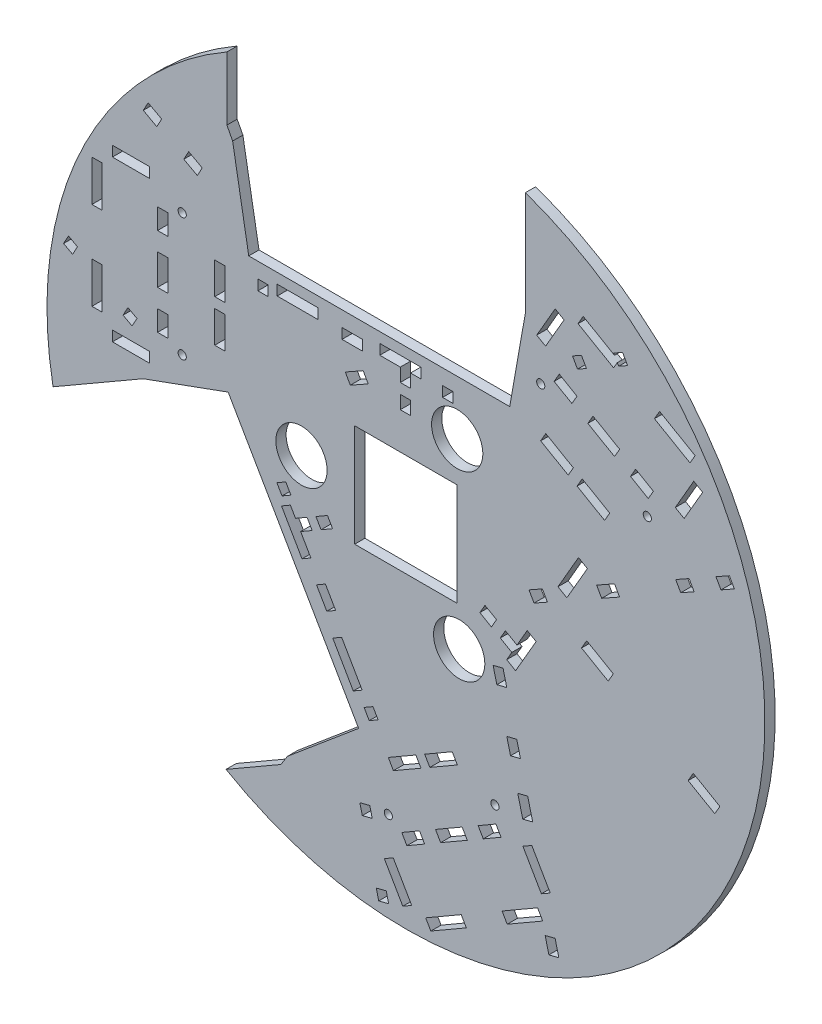
SolidWorks part; units mm, degrees
material "Balsa"
ref_plane "Plan de face" through (0, 0, 0) normal (0, 0, 1) x (1, 0, 0)
ref_plane "Plan de dessus" through (0, 0, 0) normal (0, 1, 0) x (1, 0, 0)
ref_plane "Plan de droite" through (0, 0, 0) normal (1, 0, 0) x (0, 0, -1)
sketch "Esquisse1" plane through (0, 0, 0) normal (0, 0, 1) x (1, 0, 0)
  circle A0 centre (148.0804, -12.1102) radius 175
  dimension "D1" = 350
extrude "Boss.-Extru.1" add sketch "Esquisse1" along normal blind 5
sketch "Esquisse2" plane through (0, 0, 5) normal (0, 0, 1) x (1, 0, 0)
  line L0 (135.3118, 53.7774) -> (135.3118, 48.7774)
  line L1 (5, 72.2774) -> (23, 72.2774)
  line L2 (5, 72.2774) -> (5, 67.2774)
  line L3 (5, 67.2774) -> (23, 67.2774)
  line L4 (23, 72.2774) -> (23, 67.2774)
  line L5 (-5, 62.2774) -> (0, 62.2774)
  line L6 (-5, 62.2774) -> (-5, 42.2774)
  line L7 (-5, 42.2774) -> (0, 42.2774)
  line L8 (0, 62.2774) -> (0, 42.2774)
  line L9 (-5, 19.2774) -> (0, 19.2774)
  line L10 (-5, 19.2774) -> (-5, -0.7226)
  line L11 (-5, -0.7226) -> (0, -0.7226)
  line L12 (0, 19.2774) -> (0, -0.7226)
  line L13 (5, -5.7226) -> (23, -5.7226)
  line L14 (5, -5.7226) -> (5, -10.7226)
  line L15 (5, -10.7226) -> (23, -10.7226)
  line L16 (23, -5.7226) -> (23, -10.7226)
  line L17 (27, 14.2774) -> (32, 14.2774)
  line L18 (27, 14.2774) -> (27, 4.2774)
  line L19 (27, 4.2774) -> (32, 4.2774)
  line L20 (32, 14.2774) -> (32, 4.2774)
  line L21 (27, 38.2774) -> (32, 38.2774)
  line L22 (27, 38.2774) -> (27, 23.2774)
  line L23 (27, 23.2774) -> (32, 23.2774)
  line L24 (32, 38.2774) -> (32, 23.2774)
  line L25 (27, 57.2774) -> (32, 57.2774)
  line L26 (27, 57.2774) -> (27, 47.2774)
  line L27 (27, 47.2774) -> (32, 47.2774)
  line L28 (32, 57.2774) -> (32, 47.2774)
  line L29 (54.86, 48.7774) -> (59.86, 48.7774)
  line L30 (54.86, 48.7774) -> (54.86, 33.2774)
  line L31 (54.86, 33.2774) -> (59.86, 33.2774)
  line L32 (59.86, 48.7774) -> (59.86, 33.2774)
  line L33 (54.86, 28.2774) -> (59.86, 28.2774)
  line L34 (54.86, 28.2774) -> (54.86, 12.7774)
  line L35 (54.86, 12.7774) -> (59.86, 12.7774)
  line L36 (59.86, 28.2774) -> (59.86, 12.7774)
  line L37 (85.3118, 53.7774) -> (105.3118, 53.7774)
  line L38 (85.3118, 53.7774) -> (85.3118, 48.7774)
  line L39 (85.3118, 48.7774) -> (105.3118, 48.7774)
  line L40 (105.3118, 53.7774) -> (105.3118, 48.7774)
  line L41 (145.3118, 37.2774) -> (150.3118, 37.2774)
  line L42 (145.3118, 37.2774) -> (145.3118, 30.7774)
  line L43 (145.3118, 30.7774) -> (150.3118, 30.7774)
  line L44 (150.3118, 37.2774) -> (150.3118, 30.7774)
  line L45 (135.3118, 48.7774) -> (145.3118, 48.7774)
  line L46 (155.3118, 48.7774) -> (135.3118, 48.7774) construction
  line L47 (145.3118, 48.7774) -> (145.3118, 42.2774)
  line L48 (145.3118, 42.2774) -> (150.3118, 42.2774)
  line L49 (150.3118, 42.2774) -> (150.3118, 48.7774)
  line L50 (150.3118, 48.7774) -> (155.3118, 48.7774)
  line L51 (155.3118, 48.7774) -> (155.3118, 53.7774)
  line L52 (155.3118, 53.7774) -> (135.3118, 53.7774)
  line L53 (292.7025, 69.6073) -> (283.7025, 54.0188)
  line L54 (292.7025, 69.6073) -> (288.3723, 72.1073)
  line L55 (288.3723, 72.1073) -> (279.3723, 56.5188)
  line L56 (283.7025, 54.0188) -> (279.3723, 56.5188)
  line L57 (289.0422, 83.2676) -> (286.5422, 78.9374)
  line L58 (289.0422, 83.2676) -> (271.7217, 93.2676)
  line L59 (271.7217, 93.2676) -> (269.2217, 88.9374)
  line L60 (286.5422, 78.9374) -> (269.2217, 88.9374)
  line L61 (251.8031, 104.7676) -> (249.3031, 100.4374)
  line L62 (251.8031, 104.7676) -> (234.4826, 114.7676)
  line L63 (234.4826, 114.7676) -> (231.9826, 110.4374)
  line L64 (249.3031, 100.4374) -> (231.9826, 110.4374)
  line L65 (225.1525, 108.6073) -> (216.1525, 93.0188)
  line L66 (225.1525, 108.6073) -> (220.8223, 111.1073)
  line L67 (220.8223, 111.1073) -> (211.8223, 95.5188)
  line L68 (216.1525, 93.0188) -> (211.8223, 95.5188)
  line L69 (231.473, 79.5547) -> (228.973, 75.2246)
  line L70 (231.473, 79.5547) -> (222.8127, 84.5547)
  line L71 (222.8127, 84.5547) -> (220.3127, 80.2246)
  line L72 (228.973, 75.2246) -> (220.3127, 80.2246)
  line L73 (252.2576, 67.5547) -> (249.7576, 63.2246)
  line L74 (252.2576, 67.5547) -> (239.2672, 75.0547)
  line L75 (239.2672, 75.0547) -> (236.7672, 70.7246)
  line L76 (249.7576, 63.2246) -> (236.7672, 70.7246)
  line L77 (268.7121, 58.0547) -> (266.2121, 53.7246)
  line L78 (268.7121, 58.0547) -> (260.0518, 63.0547)
  line L79 (260.0518, 63.0547) -> (257.5518, 58.7246)
  line L80 (266.2121, 53.7246) -> (257.5518, 58.7246)
  line L81 (247.4209, 38.1773) -> (244.9209, 33.8472)
  line L82 (247.4209, 38.1773) -> (233.9975, 45.9273)
  line L83 (233.9975, 45.9273) -> (231.4975, 41.5972)
  line L84 (244.9209, 33.8472) -> (231.4975, 41.5972)
  line L85 (229.6673, 48.4273) -> (227.1673, 44.0972)
  line L86 (229.6673, 48.4273) -> (216.2439, 56.1773)
  line L87 (216.2439, 56.1773) -> (213.7439, 51.8472)
  line L88 (227.1673, 44.0972) -> (213.7439, 51.8472)
  line L89 (211.5251, -33.996) -> (207.195, -31.496)
  line L90 (236.5251, 9.3053) -> (226.5251, -8.0153)
  line L91 (236.5251, 9.3053) -> (232.195, 11.8053)
  line L92 (232.195, 11.8053) -> (222.195, -5.5153)
  line L93 (226.5251, -8.0153) -> (222.195, -5.5153)
  line L94 (192.2357, -34.4063) -> (189.7357, -38.7364)
  line L95 (192.2357, -34.4063) -> (186.6065, -31.1563)
  line L96 (186.6065, -31.1563) -> (184.1065, -35.4864)
  line L97 (189.7357, -38.7364) -> (184.1065, -35.4864)
  line L98 (207.195, -31.496) -> (202.195, -40.1563)
  line L99 (202.195, -40.1563) -> (196.5658, -36.9063)
  line L100 (196.5658, -36.9063) -> (194.0658, -41.2364)
  line L101 (194.0658, -41.2364) -> (199.695, -44.4864)
  line L102 (199.695, -44.4864) -> (197.195, -48.8165)
  line L103 (197.195, -48.8165) -> (201.5251, -51.3165)
  line L104 (201.5251, -51.3165) -> (211.5251, -33.996)
  line L105 (146.5388, -178.2153) -> (137.5388, -162.6268)
  line L106 (146.5388, -178.2153) -> (150.869, -175.7153)
  line L107 (150.869, -175.7153) -> (141.869, -160.1268)
  line L108 (137.5388, -162.6268) -> (141.869, -160.1268)
  line L109 (160.1991, -181.8755) -> (157.6991, -177.5454)
  line L110 (160.1991, -181.8755) -> (177.5196, -171.8755)
  line L111 (177.5196, -171.8755) -> (175.0196, -167.5454)
  line L112 (157.6991, -177.5454) -> (175.0196, -167.5454)
  line L113 (197.4382, -160.3755) -> (194.9382, -156.0454)
  line L114 (197.4382, -160.3755) -> (214.7587, -150.3755)
  line L115 (214.7587, -150.3755) -> (212.2587, -146.0454)
  line L116 (194.9382, -156.0454) -> (212.2587, -146.0454)
  line L117 (214.0888, -139.2153) -> (205.0888, -123.6268)
  line L118 (214.0888, -139.2153) -> (218.4189, -136.7153)
  line L119 (218.4189, -136.7153) -> (209.4189, -121.1268)
  line L120 (205.0888, -123.6268) -> (209.4189, -121.1268)
  line L121 (185.7683, -130.1627) -> (183.2683, -125.8326)
  line L122 (185.7683, -130.1627) -> (194.4286, -125.1627)
  line L123 (194.4286, -125.1627) -> (191.9286, -120.8326)
  line L124 (183.2683, -125.8326) -> (191.9286, -120.8326)
  line L125 (164.9837, -142.1627) -> (162.4837, -137.8326)
  line L126 (164.9837, -142.1627) -> (177.9741, -134.6627)
  line L127 (177.9741, -134.6627) -> (175.4741, -130.3326)
  line L128 (162.4837, -137.8326) -> (175.4741, -130.3326)
  line L129 (148.5292, -151.6627) -> (146.0292, -147.3326)
  line L130 (148.5292, -151.6627) -> (157.1895, -146.6627)
  line L131 (157.1895, -146.6627) -> (154.6895, -142.3326)
  line L132 (146.0292, -147.3326) -> (154.6895, -142.3326)
  line L133 (141.9604, -123.2852) -> (139.4604, -118.9551)
  line L134 (141.9604, -123.2852) -> (155.3838, -115.5352)
  line L135 (155.3838, -115.5352) -> (152.8838, -111.2051)
  line L136 (139.4604, -118.9551) -> (152.8838, -111.2051)
  line L137 (159.7139, -113.0352) -> (157.2139, -108.7051)
  line L138 (159.7139, -113.0352) -> (173.1373, -105.2852)
  line L139 (173.1373, -105.2852) -> (170.6373, -100.9551)
  line L140 (157.2139, -108.7051) -> (170.6373, -100.9551)
  line L141 (97.4044, -56.1119) -> (101.7345, -53.6119)
  line L142 (122.4044, -99.4132) -> (112.4044, -82.0927)
  line L143 (122.4044, -99.4132) -> (126.7345, -96.9132)
  line L144 (126.7345, -96.9132) -> (116.7345, -79.5927)
  line L145 (112.4044, -82.0927) -> (116.7345, -79.5927)
  line L146 (106.6938, -39.2017) -> (104.1938, -34.8716)
  line L147 (106.6938, -39.2017) -> (112.323, -35.9517)
  line L148 (112.323, -35.9517) -> (109.823, -31.6216)
  line L149 (104.1938, -34.8716) -> (109.823, -31.6216)
  line L150 (101.7345, -53.6119) -> (96.7345, -44.9517)
  line L151 (96.7345, -44.9517) -> (102.3637, -41.7017)
  line L152 (102.3637, -41.7017) -> (99.8637, -37.3716)
  line L153 (99.8637, -37.3716) -> (94.2345, -40.6216)
  line L154 (94.2345, -40.6216) -> (91.7345, -36.2914)
  line L155 (91.7345, -36.2914) -> (87.4044, -38.7914)
  line L156 (87.4044, -38.7914) -> (97.4044, -56.1119)
  line L157 (135.3118, 53.7774) -> (135.3118, 48.7774) construction
  line L158 (105.3118, 53.7774) -> (135.3118, 53.7774) construction
  point P83 (148.0804, -12.1102)
  point P192 (148.0804, -12.1102)
  point P193 (148.0804, -12.1102)
  dimension "D1" = 3
extrude "Enlèv. mat.-Extru.1" cut sketch "Esquisse2" against normal blind 5
sketch "Esquisse6" plane through (0, 0, 5) normal (0, 0, 1) x (1, 0, 0)
  line L0 (93.9998, -7.2151) -> (100.2998, -18.127) construction
  line L1 (206.3213, 102.2219) -> (206.3213, 185.5637)
  line L2 (123.0804, -37.1102) -> (173.0804, -37.1102)
  line L3 (123.0804, -37.1102) -> (123.0804, 12.8898)
  line L4 (123.0804, 12.8898) -> (173.0804, 12.8898)
  line L5 (173.0804, -37.1102) -> (173.0804, 12.8898)
  line L6 (123.0804, -37.1102) -> (173.0804, 12.8898) construction
  line L7 (123.0804, 12.8898) -> (173.0804, -37.1102) construction
  line L8 (206.3213, 185.5637) -> (60.7972, 185.5637)
  line L9 (71.4438, 58.7774) -> (63.5848, 103.3483)
  line L10 (71.4438, 58.7774) -> (198.6608, 58.7774)
  line L11 (198.6608, 58.7774) -> (206.3213, 102.2219)
  line L12 (60.7972, 185.5637) -> (60.7972, 108.6824)
  line L13 (19.9456, -18.8381) -> (-52.2306, -60.5091)
  line L14 (-52.2306, -60.5091) -> (20.5314, -186.5366)
  line L15 (63.5848, 103.3483) -> (60.7972, 108.6824)
  line L16 (125.0083, -113.9232) -> (90.3383, -143.0148)
  line L17 (125.0083, -113.9232) -> (61.3998, -3.7501)
  line L18 (61.3998, -3.7501) -> (19.9456, -18.8381)
  line L20 (236.1714, -21.3074) -> (249.1617, -28.8074)
  line L21 (236.1714, -21.3074) -> (233.6714, -25.6375)
  line L22 (249.1617, -28.8074) -> (246.6617, -33.1375)
  line L23 (233.6714, -25.6375) -> (246.6617, -33.1375)
  line L24 (288.1329, -51.3074) -> (301.1233, -58.8074)
  line L25 (288.1329, -51.3074) -> (285.6329, -55.6375)
  line L26 (301.1233, -58.8074) -> (298.6233, -63.1375)
  line L27 (285.6329, -55.6375) -> (298.6233, -63.1375)
  line L28 (226.5251, -8.0153) -> (236.5251, 9.3053) construction
  line L29 (279.3723, 56.5188) -> (283.7025, 54.0188) construction
  line L31 (64.5427, 103.6743) -> (63.0102, 106.6067) construction
  line L32 (20.5314, -186.5366) -> (87.1126, -148.0959)
  line L33 (90.3383, -143.0148) -> (87.1126, -148.0959)
  circle A0 centre (173.06, 32.2774) radius 12.5
  circle A1 centre (174.0314, -55.9369) radius 12.5
  circle A2 centre (97.1498, -12.671) radius 12.5
  point P2 (148.0804, -12.1102)
  point P8 (148.0804, -12.1102)
  point P10 (148.0804, -12.1102)
  point P35 (148.0804, -12.1102)
  point P48 (148.0804, -12.1102)
  dimension "D12" = 25
  dimension "D3" = 50
  dimension "D4" = 50
  dimension "D5" = 70.8876
  dimension "D6" = 50.5804
  dimension "D7" = 127.217
  dimension "D8" = 100
  dimension "D9" = 100
  dimension "D10" = 145.5241
  dimension "D11" = 43.4444
  dimension "D13" = 5
  dimension "D14" = 15
  dimension "D15" = 15
  dimension "D16" = 45
  dimension "D17" = 15
  dimension "D18" = 89
  dimension "D19" = 2
  dimension "D20" = 1
  dimension "D1" = 3
extrude "Enlèv. mat.-Extru.6" cut sketch "Esquisse6" against normal blind 5
hole_wizard "Trous de centrage Ø4.0mm1" positions "Esquisse7" profile "Esquisse8" hole size "Ø4.0" standard "Ansi Metric" end condition through all
sketch "Esquisse7" plane through (148.0804, -12.1102, -78) normal (0, 0, -1) x (1, 0, 0)
  point P0 (65.7012, -88.0226)
  point P3 (117.6627, -58.0226)
  point P6 (-109.0804, -72.8876)
  point P9 (-109.0804, -12.8876)
  point P12 (-8.5823, 130.9102)
  point P15 (43.3792, 100.9102)
sketch "Esquisse8" plane through (213.7816, 75.9124, -78) normal (1, 0, 0) x (0, 1, 0)
  line L0 (0, 0) -> (0, 83)
  line L1 (0, 83) -> (2, 83)
  line L2 (2, 83) -> (2, 0)
  line L3 (2, 0) -> (0, 0)
  line L4 (0, -6.35) -> (0, 107.95) construction
  dimension "Diamètre du perçage jusqu'au prochain" = 4
  dimension "Profondeur du perçage jusqu'au prochain" = 83
sketch "Esquisse9" plane through (0, 0, 5) normal (0, 0, 1) x (1, 0, 0)
  line L0 (301.6473, 32.8747) -> (299.2005, 37.2351)
  line L1 (301.6473, 32.8747) -> (308.1879, 36.5449)
  line L2 (299.2005, 37.2351) -> (305.7411, 40.9053)
  line L3 (308.1879, 36.5449) -> (305.7411, 40.9053)
  line L4 (282.0254, 21.8642) -> (279.5786, 26.2246)
  line L5 (282.0254, 21.8642) -> (288.566, 25.5344)
  line L6 (279.5786, 26.2246) -> (286.1192, 29.8948)
  line L7 (288.566, 25.5344) -> (286.1192, 29.8948)
  line L8 (252.2089, 5.133) -> (249.7621, 9.4935)
  line L9 (252.2089, 5.133) -> (243.488, 0.2395)
  line L10 (249.7621, 9.4935) -> (241.0412, 4.5999)
  line L11 (243.488, 0.2395) -> (241.0412, 4.5999)
  line L12 (214.6084, -10.2326) -> (217.0552, -14.593)
  line L13 (214.6084, -10.2326) -> (208.0678, -13.9027)
  line L14 (217.0552, -14.593) -> (210.5146, -18.2632)
  line L15 (208.0678, -13.9027) -> (210.5146, -18.2632)
  line L16 (217.0552, -14.593) -> (243.488, 0.2395) construction
  line L17 (214.6084, -10.2326) -> (217.0552, -14.593) construction
  line L18 (256.1275, 104.7997) -> (251.7671, 102.3529)
  line L19 (256.1275, 104.7997) -> (253.6807, 109.1601)
  line L20 (251.7671, 102.3529) -> (249.3203, 106.7133)
  line L21 (253.6807, 109.1601) -> (249.3203, 106.7133)
  line L22 (236.0696, 93.5445) -> (231.7091, 91.0977)
  line L23 (236.0696, 93.5445) -> (233.6228, 97.9049)
  line L24 (231.7091, 91.0977) -> (229.2624, 95.4581)
  line L25 (233.6228, 97.9049) -> (229.2624, 95.4581)
  line L26 (129.6754, 33.8428) -> (120.9546, 28.9492)
  line L27 (129.6754, 33.8428) -> (127.2286, 38.2032)
  line L28 (120.9546, 28.9492) -> (118.5078, 33.3096)
  line L29 (127.2286, 38.2032) -> (118.5078, 33.3096)
  line L30 (256.1275, 104.7997) -> (120.9546, 28.9492) construction
  line L31 (301.6473, 32.8747) -> (217.0552, -14.593) construction
  line L32 (-16.4384, 23.2791) -> (-12.0459, 20.8904)
  line L33 (-16.4384, 23.2791) -> (-18.8272, 18.8866)
  line L34 (-12.0459, 20.8904) -> (-14.4347, 16.4979)
  line L35 (-18.8272, 18.8866) -> (-14.4347, 16.4979)
  line L36 (12.552, 7.5136) -> (16.9445, 5.1249)
  line L37 (12.552, 7.5136) -> (10.1633, 3.1211)
  line L38 (16.9445, 5.1249) -> (14.5558, 0.7324)
  line L39 (10.1633, 3.1211) -> (14.5558, 0.7324)
  line L42 (-26.9196, -12.1102) -> (148.0804, -12.1102) construction
  line L44 (22.4127, 98.9071) -> (29.0015, 95.324)
  line L45 (22.4127, 98.9071) -> (20.024, 94.5146)
  line L46 (29.0015, 95.324) -> (26.6128, 90.9315)
  line L47 (20.024, 94.5146) -> (26.6128, 90.9315)
  line L48 (42.179, 88.1579) -> (48.7677, 84.5748)
  line L49 (42.179, 88.1579) -> (39.7903, 83.7654)
  line L50 (48.7677, 84.5748) -> (46.379, 80.1823)
  line L51 (39.7903, 83.7654) -> (46.379, 80.1823)
  line L53 (148.0804, -12.1102) -> (9.6568, -109.2191) construction
  line L55 (129.7636, 187.6323) -> (148.0804, -12.1102) construction
  arc A0 (60.3638, -163.5394) -> (206.3213, 152.9141) centre (148.0804, -12.1102) ccw construction
  line B0 (154.106, -73.5915) -> (185.6214, -199.5155) construction
  line B1 (126.7996, -149.8343) -> (125.5857, -144.9839)
  line B2 (130.4361, -143.77) -> (125.5857, -144.9839)
  line B3 (131.65, -148.6204) -> (126.7996, -149.8343)
  line B4 (131.65, -148.6204) -> (130.4361, -143.77)
  line B5 (134.8115, -181.8469) -> (133.5976, -176.9965)
  line B6 (138.448, -175.7826) -> (133.5976, -176.9965)
  line B7 (139.6619, -180.633) -> (134.8115, -181.8469)
  line B8 (139.6619, -180.633) -> (138.448, -175.7826)
  line B9 (190.562, -54.5014) -> (195.4124, -53.2875)
  line B10 (197.2333, -60.5631) -> (195.4124, -53.2875)
  line B11 (192.3829, -61.777) -> (190.562, -54.5014)
  line B12 (192.3829, -61.777) -> (197.2333, -60.5631)
  line B13 (202.089, -79.9647) -> (197.2386, -81.1786)
  line B14 (199.0595, -88.4542) -> (197.2386, -81.1786)
  line B15 (203.9099, -87.2403) -> (202.089, -79.9647)
  line B16 (203.9099, -87.2403) -> (199.0595, -88.4542)
  line B17 (222.6043, -161.9364) -> (217.7539, -163.1503)
  line B18 (215.933, -155.8747) -> (217.7539, -163.1503)
  line B19 (220.7834, -154.6608) -> (222.6043, -161.9364)
  line B20 (220.7834, -154.6608) -> (215.933, -155.8747)
  dimension "D9" = 170.2546
  dimension "D1" = 10
  dimension "D2" = 5
  dimension "D3" = 7.5
  dimension "D4" = 10
  dimension "D5" = 7.5
  dimension "D6" = 7.5
  dimension "D7" = 5
  dimension "D8" = 117
  dimension "D10" = 167.3371
  dimension "D11" = 69
  dimension "D12" = 35.051
  dimension "D13" = 30.31
  dimension "D14" = 5
sketch_block_instance "Bloc1-1"
sketch_block "Bloc1"
extrude "Holes catchers of glass" cut sketch "Esquisse9" against normal blind 10
sketch "Esquisse10" plane through (0, 0, 5) normal (0, 0, 1) x (1, 0, 0)
  line L0 (89.4961, -27.6144) -> (91.9961, -31.9445)
  line L1 (89.4961, -27.6144) -> (85.1672, -30.1137)
  line L2 (91.9961, -31.9445) -> (87.6672, -34.4438)
  line L3 (85.1672, -30.1137) -> (87.6672, -34.4438)
  dimension "D1" = 4.9986
extrude "Holes boards servo" cut sketch "Esquisse10" against normal blind 10
sketch "Esquisse11" plane through (0, 0, 5) normal (0, 0, 1) x (1, 0, 0)
  line L0 (109.4829, -72.2325) -> (104.4829, -63.5722)
  line L1 (109.4829, -72.2325) -> (113.813, -69.7325)
  line L2 (104.4829, -63.5722) -> (108.813, -61.0722)
  line L3 (113.813, -69.7325) -> (108.813, -61.0722)
  line L4 (125.166, -99.3964) -> (90.166, -38.7747) construction
  line L6 (116.7345, -79.5927) -> (112.4044, -82.0927) construction
  line L7 (130.166, -108.0567) -> (134.4961, -105.5567)
  line L8 (130.166, -108.0567) -> (127.666, -103.7266)
  line L9 (134.4961, -105.5567) -> (131.9961, -101.2266)
  line L10 (127.666, -103.7266) -> (131.9961, -101.2266)
  line L11 (207.4302, -101.3064) -> (209.8581, -111.0072)
  line L12 (170.9253, 51.2774) -> (165.9253, 51.2774)
  line L13 (170.9253, 51.2774) -> (170.9253, 46.2774)
  line L14 (170.9253, 46.2774) -> (165.9253, 46.2774)
  line L15 (165.9253, 51.2774) -> (165.9253, 46.2774)
  line L16 (126.9253, 51.2774) -> (116.9253, 51.2774)
  line L17 (126.9253, 51.2774) -> (126.9253, 46.2774)
  line L18 (126.9253, 46.2774) -> (116.9253, 46.2774)
  line L19 (116.9253, 51.2774) -> (116.9253, 46.2774)
  line L20 (80.9253, 51.2774) -> (75.9253, 51.2774)
  line L21 (80.9253, 51.2774) -> (80.9253, 46.2774)
  line L22 (80.9253, 46.2774) -> (75.9253, 46.2774)
  line L23 (75.9253, 51.2774) -> (75.9253, 46.2774)
  line L24 (207.4302, -101.3064) -> (202.5798, -102.5203)
  line L25 (209.8581, -111.0072) -> (205.0077, -112.2211)
  line L26 (202.5798, -102.5203) -> (205.0077, -112.2211)
  line L27 (203.9099, -87.2403) -> (202.089, -79.9647) construction
  line L28 (220.7834, -154.6608) -> (215.933, -155.8747) construction
  dimension "D1" = 10
  dimension "D2" = 10
  dimension "D3" = 5
  dimension "D4" = 5
  dimension "D5" = 5
  dimension "D6" = 10
  dimension "D7" = 45
extrude "Enlèv. mat.-Extru.7" cut sketch "Esquisse11" against normal blind 5
